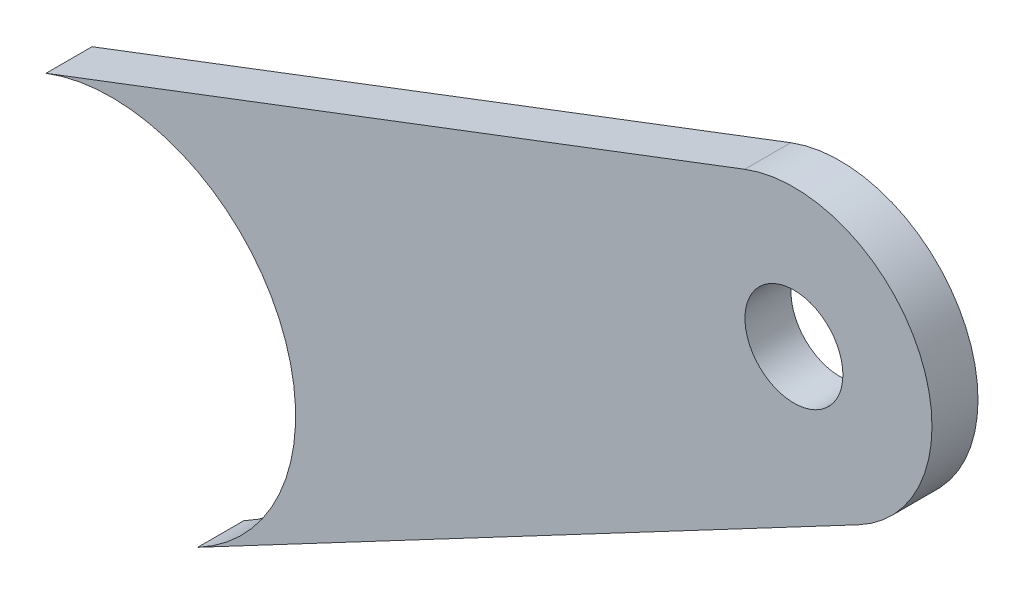
SolidWorks part; units mm, degrees
ref_plane "Front Plane" through (0, 0, 0) normal (0, 0, 1) x (1, 0, 0)
ref_plane "Top Plane" through (0, 0, 0) normal (0, 1, 0) x (1, 0, 0)
ref_plane "Right Plane" through (0, 0, 0) normal (1, 0, 0) x (0, 0, -1)
sketch "Sketch1" plane through (0, 0, 0) normal (0, 0, 1) x (1, 0, 0)
  line L0 (-101.5644, 0) -> (-148.6434, -21.3358) construction
  line L1 (-101.5644, 0) -> (-148.6434, -21.3358)
  line L2 (-153.1652, -9.4681) -> (-104.9558, 8.9008)
  line L3 (-142.7004, -32.5595) -> (-97.1072, -8.4178)
  circle A0 centre (-101.5644, 0) radius 3.3782 construction
  circle A1 centre (-101.5644, 0) radius 3.3782
  circle A2 centre (-101.5644, 0) radius 9.525
  circle A3 centre (-148.6434, -21.3358) radius 12.7
  dimension "D1" = 19.05
  dimension "D2" = 25.4
extrude "Boss-Extrude1" add sketch "Sketch1" along normal blind 3.175 contours A2 A1 | A3 L1 A2 L2 | A3 L3 A2 L1 region at (-110.1228, 3.5242, 0) region at (-121.8438, -15.7464, 0) region at (-126.7736, -4.8686, 0)
